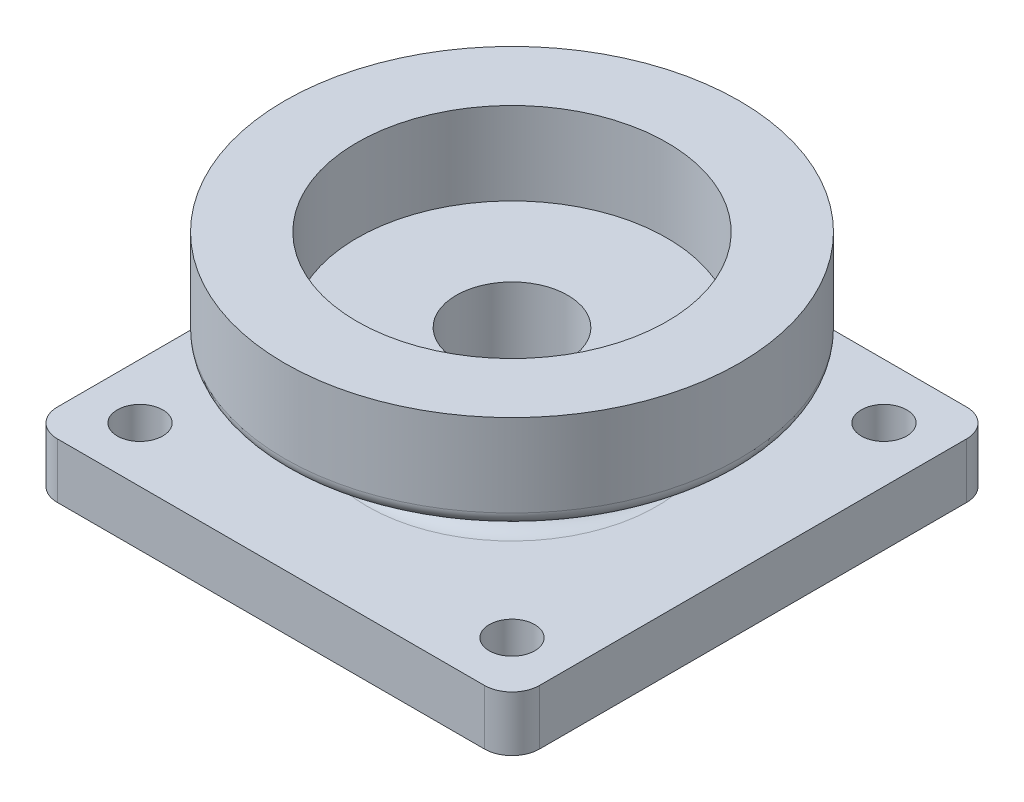
SolidWorks part; units mm, degrees
note: The reader was unsure of these and kept them because the rebuilt part matched: shared geometry of "Croquis1<8>", "Croquis2<3>".
ref_plane "Front Plane" through (0, 0, 0) normal (0, 0, 1) x (1, 0, 0)
ref_plane "Top Plane" through (0, 0, 0) normal (0, 1, 0) x (1, 0, 0)
ref_plane "Right Plane" through (0, 0, 0) normal (1, 0, 0) x (0, 0, -1)
sketch "Croquis1" plane through (0, 0, 0) normal (0, 1, 0) x (1, 0, 0)
  line L1 (-17.5, 17.5) -> (17.5, 17.5)
  line L2 (-17.5, 17.5) -> (-17.5, -17.5)
  line L3 (-17.5, -17.5) -> (17.5, -17.5)
  line L4 (17.5, 17.5) -> (17.5, -17.5)
  line L5 (-17.5, 17.5) -> (17.5, -17.5) construction
  line L6 (-17.5, -17.5) -> (17.5, 17.5) construction
  circle A4 centre (-13.5, -13.5) radius 1.65
  circle A5 centre (13.5, -13.5) radius 1.65
  circle A6 centre (13.5, 13.5) radius 1.65
  circle A7 centre (-13.5, 13.5) radius 1.65
  circle A8 centre (0, 0) radius 4.05
  circle A9 centre (0, 0) radius 9
  point P0 (0, 0)
  dimension "D4" = 18
  dimension "D6" = 3.3
  dimension "D1" = 8.1
  dimension "D2" = 35
  dimension "D3" = 35
  dimension "D7" = 13.5
extrude "Saliente-Extruir1" add sketch "Croquis1" along normal blind 4
fillet "Redondeo2" radius 2 4 edges at (17.5, 2, -17.5) (-17.5, 2, -17.5) (17.5, 2, 17.5) (-17.5, 2, 17.5)
extrude "Saliente-Extruir2" add sketch "Croquis1<8>" along normal blind 9 contours A9 A8
sketch "Croquis1<8>" plane through (0, 0, 0) normal (0, 1, 0) x (1, 0, 0) same geometry as "Croquis1"
sketch "Croquis2" plane through (0, 9, 0) normal (0, 1, 0) x (1, 0, 0)
  circle A0 centre (0, 0) radius 11.25
  circle A1 centre (0, 0) radius 16.5
  circle M2 centre (0, 0) radius 4.05
  circle M3 centre (0, 0) radius 9
  dimension "D1" = 22.5
  dimension "D2" = 33
extrude "Saliente-Extruir3" add sketch "Croquis2" along normal blind 7 separate body
fillet "Redondeo3" radius 1.5 1 edges at (0, 4, 9)
extrude "Saliente-Extruir4" add sketch "Croquis2<3>" along normal blind 1 contours A0 M3 | M3 M2
sketch "Croquis2<3>" plane through (0, 9, 0) normal (0, 1, 0) x (1, 0, 0) same geometry as "Croquis2"
fillet "Redondeo4" radius 1.5 1 edges at (0, 9, 9)
fillet "Redondeo5" radius 1 1 edges at (0, 9, 16.5)
